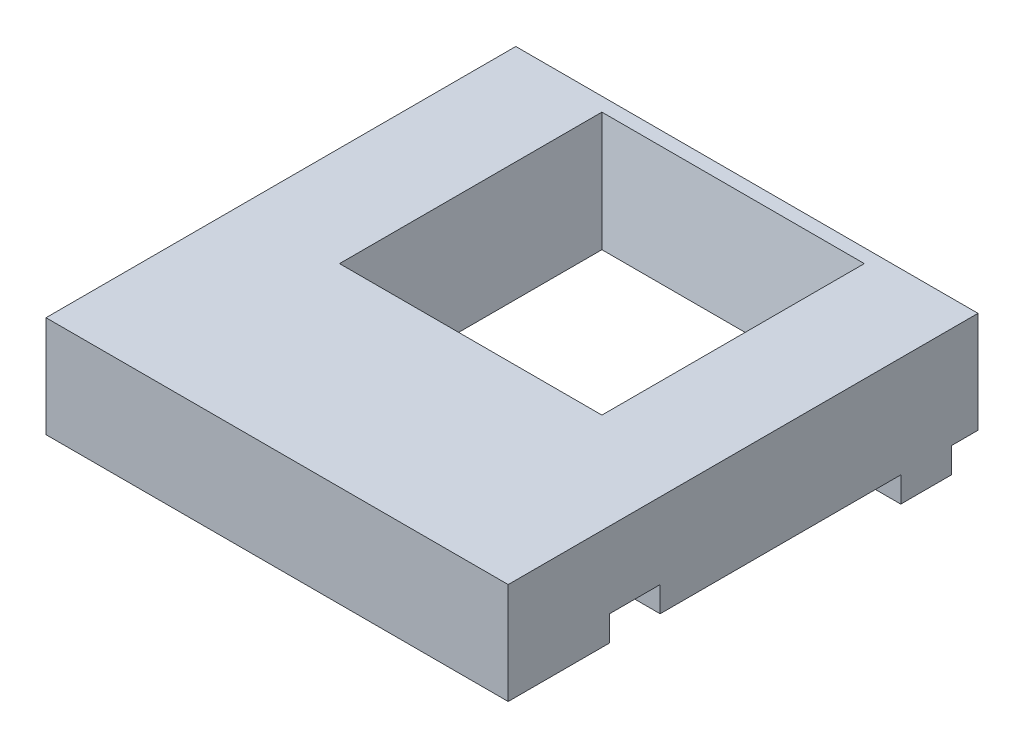
SolidWorks part; units mm, degrees
ref_plane "Front Plane" through (0, 0, 0) normal (0, 0, 1) x (1, 0, 0)
ref_plane "Top Plane" through (0, 0, 0) normal (0, 1, 0) x (1, 0, 0)
ref_plane "Right Plane" through (0, 0, 0) normal (1, 0, 0) x (0, 0, -1)
sketch "Sketch1" plane through (0, 0, 0) normal (0, 1, 0) x (1, 0, 0)
  line L1 (0, 0) -> (36.5, 0)
  line L2 (0, 0) -> (0, -37.1)
  line L3 (0, -37.1) -> (36.5, -37.1)
  line L4 (36.5, 0) -> (36.5, -37.1)
  dimension "D1" = 37.1
  dimension "D2" = 36.5
extrude "Body" add sketch "Sketch1" along normal blind 8
sketch "Sketch2" plane through (0, 0, 0) normal (0, -1, 0) x (-1, 0, 0)
  line L0 (-36.5, 0) -> (0, 0) construction
  line L1 (0, -6.1) -> (-2, -6.1)
  line L2 (0, -6.1) -> (0, -2.1)
  line L3 (0, -2.1) -> (-2, -2.1)
  line L4 (-2, -6.1) -> (-2, -2.1)
  line L5 (-34.5, -29.1) -> (-36.5, -29.1)
  line L6 (-34.5, -29.1) -> (-34.5, -25.1)
  line L7 (-34.5, -25.1) -> (-36.5, -25.1)
  line L8 (-36.5, -29.1) -> (-36.5, -25.1)
  line L10 (0, 0) -> (0, -37.1) construction
  line L11 (0, -37.1) -> (-36.5, -37.1) construction
  line L13 (-36.5, -37.1) -> (-36.5, 0) construction
  point P10 (-1, -2.1)
  dimension "D1" = 2.1
  dimension "D2" = 4
  dimension "D3" = 2
  dimension "D4" = 8
  dimension "D5" = 4
  dimension "D6" = 2
extrude "Female Tabs" cut sketch "Sketch2" against normal blind 2
sketch "Sketch3" plane through (0, 0, 0) normal (0, -1, 0) x (-1, 0, 0)
  line L0 (-36.5, -29.1) -> (-34.5, -29.1) construction
  line L1 (0, -29.1) -> (-2, -29.1)
  line L2 (0, -29.1) -> (0, -25.1)
  line L3 (0, -25.1) -> (-2, -25.1)
  line L4 (-2, -29.1) -> (-2, -25.1)
  line L5 (-34.5, -6.1) -> (-36.5, -6.1)
  line L6 (-34.5, -6.1) -> (-34.5, -2.1)
  line L7 (-34.5, -2.1) -> (-36.5, -2.1)
  line L8 (-36.5, -6.1) -> (-36.5, -2.1)
  line L9 (0, -6.1) -> (0, -37.1) construction
  line L10 (-36.5, -25.1) -> (-36.5, 0) construction
  line L11 (0, -2.1) -> (-2, -2.1) construction
  dimension "D1" = 2
  dimension "D2" = 4
  dimension "D3" = 2
  dimension "D4" = 4
extrude "Male Tabs" add sketch "Sketch3" along normal blind 2
sketch "Sketch5" plane through (0, 0, 0) normal (0, -1, 0) x (-1, 0, 0)
  line L0 (-36.5, 0) -> (0, 0) construction
  line L1 (-27.2, -2.5) -> (-9.3, -2.5)
  line L2 (-27.2, -2.5) -> (-27.2, -20.4)
  line L3 (-27.2, -20.4) -> (-9.3, -20.4)
  line L4 (-9.3, -2.5) -> (-9.3, -20.4)
  line L5 (-36.5, -2.1) -> (-36.5, 0) construction
  line L6 (0, -6.1) -> (0, -25.1) construction
  line L7 (0, -37.1) -> (-36.5, -37.1) construction
  dimension "D1" = 2.5
  dimension "D2" = 9.3
  dimension "D3" = 9.3
  dimension "D4" = 16.7
extrude "SiPM Window" cut sketch "Sketch5" against normal up to next (8 mm away) draft 10 draft outward yes
sketch "Sketch6" plane through (0, 0, 0) normal (0, -1, 0) x (1, 0, 0)
  line L0 (36.5, 0) -> (0, 0) construction
  line L1 (34, 1.5) -> (29.2, 1.5)
  line L2 (34, 1.5) -> (34, 35.1)
  line L4 (29.2, 1.5) -> (29.2, 22.4)
  line L5 (29.2, 22.4) -> (7.3, 22.4)
  line L9 (7.3, 1.5) -> (2.5, 1.5)
  line L10 (7.3, 1.5) -> (7.3, 22.4)
  line L13 (36.5, 25.1) -> (36.5, 6.1) construction
  line L16 (34, 35.1) -> (2.5, 35.1)
  line L17 (2.5, 35.1) -> (2.5, 1.5)
  line L18 (0, 6.1) -> (0, 25.1) construction
  line L19 (0, 37.1) -> (36.5, 37.1) construction
  line L20 (27.2, 20.4) -> (9.3, 20.4) construction
  line L21 (9.3, 20.4) -> (9.3, 2.5) construction
  line L22 (27.2, 2.5) -> (27.2, 20.4) construction
  dimension "D1" = 1.5
  dimension "D2" = 1.5
  dimension "D3" = 2.5
  dimension "D4" = 2.5
  dimension "D5" = 2
  dimension "D6" = 2
  dimension "D7" = 2
  dimension "D8" = 2
extrude "Cut-Extrude2" cut sketch "Sketch6" against normal offset from surface (6 mm away) 2 up to face at (18.25, 8, 11.45)
